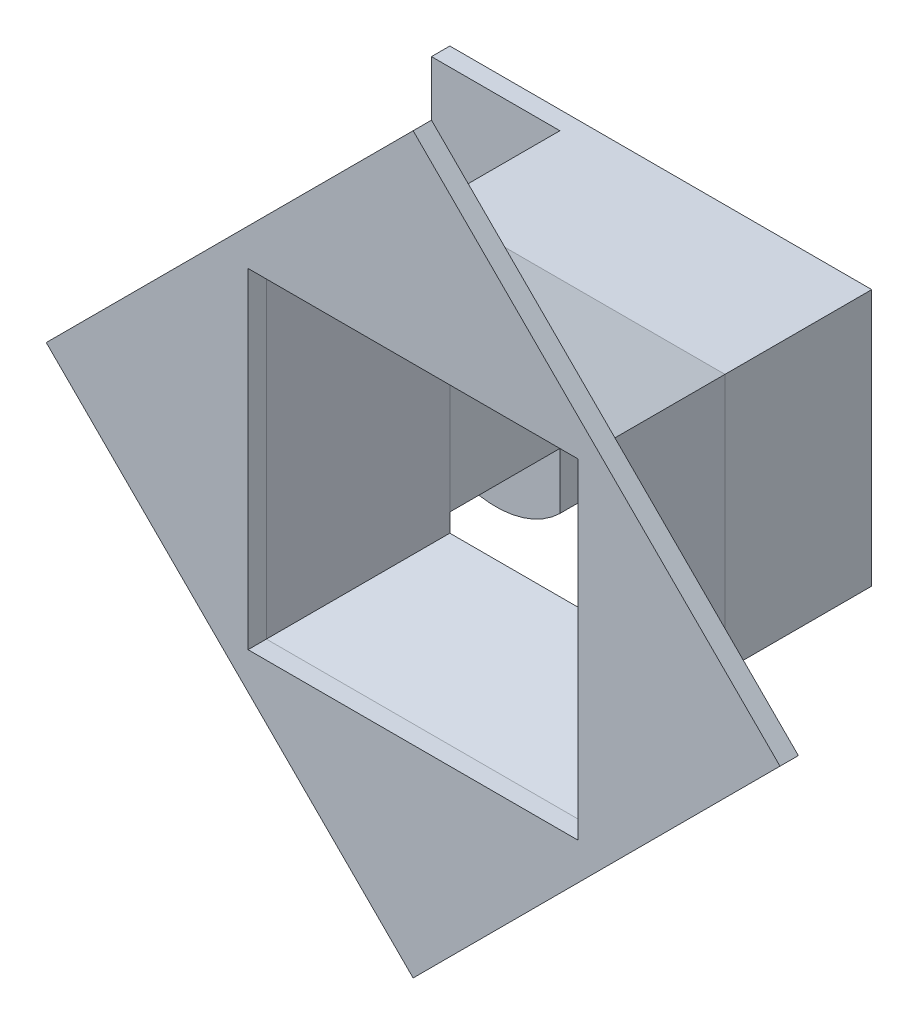
SolidWorks part; units mm, degrees
material "ABS"
ref_plane "Front Plane" through (0, 0, 0) normal (0, 0, 1) x (1, 0, 0)
ref_plane "Top Plane" through (0, 0, 0) normal (0, 1, 0) x (1, 0, 0)
ref_plane "Right Plane" through (0, 0, 0) normal (1, 0, 0) x (0, 0, -1)
sketch "Sketch2" plane through (0, 0, 0) normal (0, 0, 1) x (1, 0, 0)
  line L0 (0, 0) -> (69.8407, 0) construction
  line L1 (-50.8, 50.8) -> (50.8, 50.8)
  line L2 (-50.8, 50.8) -> (-50.8, -50.8)
  line L3 (-50.8, -50.8) -> (50.8, -50.8)
  line L4 (50.8, 50.8) -> (50.8, -50.8)
  line L5 (0, 0) -> (0, -80.5593) construction
  dimension "D1" = 101.6
ref_plane "Plane1" through (0, 0, 50.8) normal (0, 0, 1) x (1, 0, 0)
sketch "Sketch3" plane through (0, 0, 50.8) normal (0, 0, 1) x (1, 0, 0)
  line L0 (0, 0) -> (0, 42.9934) construction
  line L1 (-63.5, 63.5) -> (63.5, 63.5)
  line L2 (-63.5, 63.5) -> (-63.5, -63.5)
  line L3 (-63.5, -63.5) -> (63.5, -63.5)
  line L4 (63.5, 63.5) -> (63.5, -63.5)
  line L7 (0, 0) -> (38.1349, 0) construction
  dimension "D1" = 127
loft "Loft1" add profiles "Sketch2", "Sketch3" connector at (50.8, 50.8, 0) connector at (63.5, 63.5, 50.8)
sketch "Sketch4" plane through (0, 0, 50.8) normal (0, 0, 1) x (1, 0, 0)
  line L14 (-57.15, -57.15) -> (57.15, -57.15)
  line L15 (57.15, -57.15) -> (57.15, 57.15)
  line L16 (57.15, 57.15) -> (-57.15, 57.15)
  line L17 (-57.15, 57.15) -> (-57.15, -57.15)
  line L18 (-57.15, -57.15) -> (57.15, -57.15)
  line L19 (57.15, -57.15) -> (57.15, 57.15)
  line L20 (57.15, 57.15) -> (-57.15, 57.15)
  line L21 (-57.15, 57.15) -> (-57.15, -57.15)
  dimension "D1" = 6.35
sketch "Sketch5" plane through (0, 0, 0) normal (0, 0, -1) x (-1, 0, 0)
  line L14 (-44.45, -44.45) -> (44.45, -44.45)
  line L15 (44.45, -44.45) -> (44.45, 44.45)
  line L16 (44.45, 44.45) -> (-44.45, 44.45)
  line L17 (-44.45, 44.45) -> (-44.45, -44.45)
  line L18 (-44.45, -44.45) -> (44.45, -44.45)
  line L19 (44.45, -44.45) -> (44.45, 44.45)
  line L20 (44.45, 44.45) -> (-44.45, 44.45)
  line L21 (-44.45, 44.45) -> (-44.45, -44.45)
  dimension "D1" = 6.35
loft "Cut-Loft1" cut profiles "Sketch5", "Sketch4" connector at (-44.45, 44.45, 0) connector at (-57.15, 57.15, 50.8)
sketch "Sketch6" plane through (0, 0, 0) normal (0, 0, -1) x (-1, 0, 0)
  line L0 (44.45, -38.1) -> (50.8, -38.1)
  line L1 (44.45, -44.45) -> (44.45, 44.45) construction
  line L2 (50.8, 50.8) -> (50.8, -50.8) construction
  line L3 (50.8, -38.1) -> (50.8, 50.8)
  line L4 (50.8, 50.8) -> (-50.8, 50.8)
  line L5 (-50.8, 50.8) -> (-50.8, -38.1)
  line L6 (-50.8, -50.8) -> (-50.8, 50.8) construction
  line L7 (-50.8, -38.1) -> (-44.45, -38.1)
  line L8 (-44.45, 44.45) -> (-44.45, -44.45) construction
  line L9 (-44.45, -38.1) -> (-44.45, 44.45)
  line L10 (-44.45, 44.45) -> (44.45, 44.45)
  line L11 (44.45, 44.45) -> (44.45, -38.1)
  line L13 (-44.45, -38.1) -> (-38.1, -38.1) construction
extrude "Boss-Extrude1" add sketch "Sketch6" along normal blind 50.8
sketch "Sketch7" plane through (0, 0, -50.8) normal (0, 0, -1) x (-1, 0, 0)
  line L0 (50.8, 50.8) -> (-50.8, 50.8) construction
  line L1 (44.45, -38.1) -> (95.25, -38.1)
  line L2 (44.45, -38.1) -> (44.45, 50.8)
  line L3 (44.45, 50.8) -> (95.25, 50.8)
  line L4 (95.25, -38.1) -> (95.25, 50.8)
  dimension "D1" = 50.8
extrude "Boss-Extrude2" add sketch "Sketch7" against normal blind 6.35
sketch "Sketch8" plane through (0, 0, -44.45) normal (0, 0, 1) x (1, 0, 0)
  line L0 (-50.8, 50.8) -> (-50.8, -38.1) construction
  line L1 (-95.25, -38.1) -> (-50.8, -38.1)
  line L2 (-95.25, -38.1) -> (-95.25, -76.2)
  line L3 (-95.25, -76.2) -> (-50.8, -76.2)
  line L4 (-50.8, -38.1) -> (-50.8, -76.2)
  dimension "D1" = 38.1
extrude "Boss-Extrude3" add sketch "Sketch8" against normal up to surface (6.35 mm away) up to face at (-11.1125, 4.7625, -50.8)
fillet "Fillet1" [suppressed] radius 35.56
sketch "Sketch9" plane through (0, 0, -44.45) normal (0, 0, 1) x (1, 0, 0)
  line L0 (-73.025, 27.6092) -> (-73.025, -57.5144) construction
  line L3 (-62.992, -50.3) -> (-62.992, -11.041) construction
  line L4 (-83.185, -10.3505) -> (-62.865, -10.3505)
  line L5 (-83.185, -10.3505) -> (-83.185, -50.9905)
  line L6 (-83.185, -50.9905) -> (-62.865, -50.9905)
  line L7 (-62.865, -10.3505) -> (-62.865, -50.9905)
  line L8 (-83.058, -11.041) -> (-83.058, -50.3) construction
  line L9 (-89.9768, -30.6705) -> (-55.7405, -30.6705) construction
  line L10 (-82.558, -50.8) -> (-63.492, -50.8) construction
  line L11 (-63.492, -10.541) -> (-82.558, -10.541) construction
  dimension "D1" = 20.32
  dimension "D2" = 40.64
fillet "Fillet2" [suppressed] radius 2.54
extrude "Cut-Extrude1" cut sketch "Sketch9" against normal through all
sketch "Sketch10" plane through (0, 0, -44.45) normal (0, 0, 1) x (1, 0, 0)
  circle A0 centre (-68.025, -6.1705) radius 1.778
  circle A1 centre (-78.025, -6.1705) radius 1.778
  circle A2 centre (-78.025, -55.1705) radius 1.778
  circle A3 centre (-68.025, -55.1705) radius 1.778
  arc A4 (-76.755, -56.4148) -> (-79.295, -56.4148) centre (-78.025, -55.1705) ccw construction
  arc A5 (-66.755, -56.4148) -> (-69.295, -56.4148) centre (-68.025, -55.1705) ccw construction
  arc A6 (-79.295, -4.9262) -> (-76.755, -4.9262) centre (-78.025, -6.1705) ccw construction
  arc A7 (-69.295, -4.9262) -> (-66.755, -4.9262) centre (-68.025, -6.1705) ccw construction
extrude "Cut-Extrude2" cut sketch "Sketch10" against normal through all
sketch "Sketch11" plane through (0, 0, -44.45) normal (0, 0, 1) x (1, 0, 0)
  line L0 (-50.8, -76.2) -> (-95.25, -76.2)
  line L1 (-95.25, -76.2) -> (-50.8, -76.2) construction
  line L2 (-95.25, -76.2) -> (-95.25, -63.949)
  line L3 (-95.25, -76.2) -> (-95.25, 50.8) construction
  line L4 (-50.8, -76.2) -> (-50.8, -63.949)
  line L5 (-50.8, -76.2) -> (-50.8, -38.1) construction
  circle A0 centre (-73.025, -41.275) radius 31.75
  circle A1 centre (-73.025, -41.275) radius 6.25 construction
  line M11 (-95.25, 50.8) -> (-95.25, -76.2)
  line M12 (-95.25, -76.2) -> (-50.8, -76.2)
  line M13 (-50.8, -76.2) -> (-50.8, -38.1)
  dimension "D1" = 63.5
extrude "Cut-Extrude3" cut sketch "Sketch11" against normal blind 6.35 contours A0 M11 M12 M13 region at (-73.025, -75.7389, -44.45)
sketch "Sketch12" plane through (0, 0, 50.8) normal (0, 0, 1) x (1, 0, 0)
  line L0 (127, 0) -> (0, -127)
  line L1 (127, 0) -> (0, 127)
  line L2 (0, -127) -> (-127, 0)
  line L3 (0, 127) -> (-127, 0)
  line L4 (-63.5, -63.5) -> (63.5, -63.5) construction
  line L5 (0, 0) -> (-106.6892, -106.6892) construction
  line L6 (0, 0) -> (125.9109, -125.9109) construction
  line L7 (63.5, -63.5) -> (63.5, 63.5) construction
  line L8 (-63.5, 63.5) -> (-63.5, -63.5) construction
  line L9 (63.5, 63.5) -> (-63.5, 63.5) construction
  line L10 (63.5, -63.5) -> (63.5, 63.5)
  line L11 (-63.5, -63.5) -> (63.5, -63.5)
  line L12 (-63.5, 63.5) -> (-63.5, -63.5)
  line L13 (63.5, 63.5) -> (-63.5, 63.5)
  line L14 (57.15, -57.15) -> (57.15, 57.15) construction
  line L15 (-57.15, -57.15) -> (57.15, -57.15) construction
  line L16 (-57.15, 57.15) -> (-57.15, -57.15) construction
  line L17 (57.15, 57.15) -> (-57.15, 57.15) construction
  line L18 (57.15, -57.15) -> (57.15, 57.15)
  line L19 (-57.15, -57.15) -> (57.15, -57.15)
  line L20 (-57.15, 57.15) -> (-57.15, -57.15)
  line L21 (57.15, 57.15) -> (-57.15, 57.15)
  line M11 (57.15, -57.15) -> (-57.15, -57.15)
  line M12 (-57.15, -57.15) -> (-57.15, 57.15)
  line M13 (-57.15, 57.15) -> (57.15, 57.15)
  line M14 (57.15, 57.15) -> (57.15, -57.15)
  dimension "D1" = 45
extrude "Boss-Extrude5" add sketch "Sketch12" along normal blind 6.35 contours L0 L1 | M14 M11 M12 M13 | L2 L0 | L3 L2 | L1 L3 region at (84.6667, 0, 50.8) region at (0, -61.7039, 50.8) region at (0, -84.6667, 50.8) region at (0, 84.6667, 50.8) region at (-84.6667, 0, 50.8)
